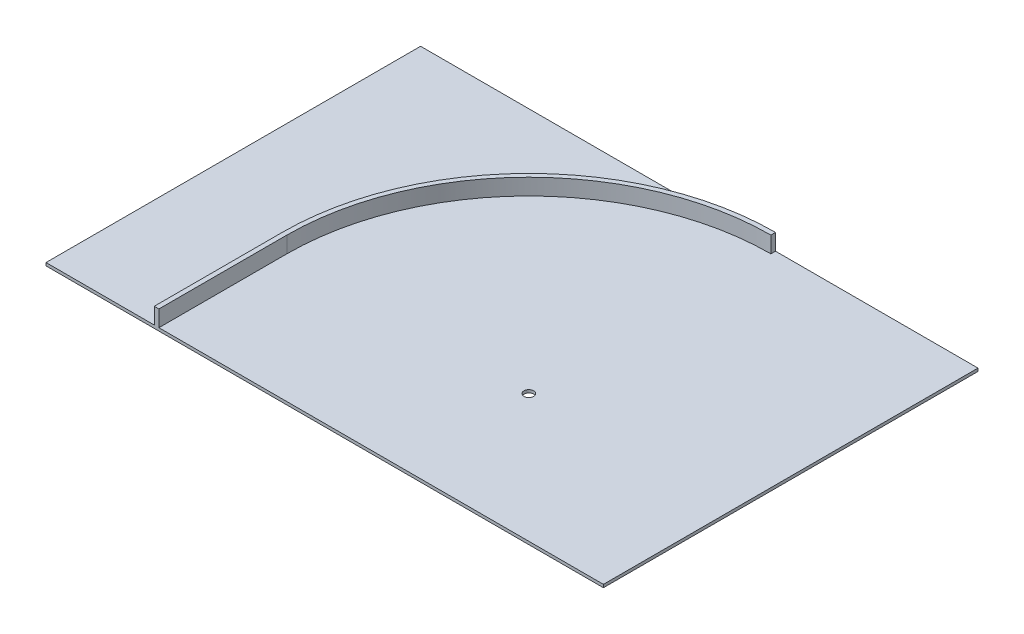
SolidWorks part; units mm, degrees
ref_plane "Front Plane" through (0, 0, 0) normal (0, 0, 1) x (1, 0, 0)
ref_plane "Top Plane" through (0, 0, 0) normal (0, 1, 0) x (1, 0, 0)
ref_plane "Right Plane" through (0, 0, 0) normal (1, 0, 0) x (0, 0, -1)
sketch "Sketch3" plane through (0, 0, 0) normal (0, 1, 0) x (1, 0, 0)
  line L0 (0, 521) -> (0, 531)
  line L1 (0, 0) -> (-839.8654, 0) construction
  line L2 (0, 0) -> (-451.1992, 260.5) construction
  line L5 (-521, 0) -> (-531, 0)
  circle A0 centre (0, 0) radius 250 construction
  arc A3 (0, 521) -> (-521, 0) centre (0, 0) ccw
  arc A4 (0, 531) -> (-531, 0) centre (0, 0) ccw
  dimension "D1" = 521
  dimension "D2" = 10
  dimension "D3" = 30
extrude "Boss-Extrude1" add sketch "Sketch3" along normal blind 35
sketch "Sketch4" plane through (0, 0, 0) normal (0, 1, 0) x (1, 0, 0)
  line L1 (-764.07, -275.4) -> (435.93, -275.4)
  line L2 (-764.07, -275.4) -> (-764.07, 531)
  line L3 (-764.07, 531) -> (435.93, 531)
  line L4 (435.93, -275.4) -> (435.93, 531)
  dimension "D1" = 1200
  dimension "D2" = 275.4
  dimension "D3" = 764.07
extrude "Boss-Extrude2" add sketch "Sketch4" against normal blind 6.35
hole_wizard "Ø20.0mm Dowel Hole1" positions "Sketch6" profile "Sketch7" hole size "Ø20.0" standard "ANSI Metric" end condition through all
sketch "Sketch6" plane through (0, 0, 0) normal (0, 1, 0) x (1, 0, 0)
  point P0 (0, 0)
sketch "Sketch7" plane through (0, 0, 0) normal (1, 0, 0) x (0, 0, 1)
  line L0 (0, 0) -> (0, 6.35)
  line L1 (0, 6.35) -> (10.5, 6.35)
  line L2 (10.5, 6.35) -> (10.5, 0)
  line L5 (10.5, 0) -> (0, 0)
  line L11 (0, -6.35) -> (0, 107.95) construction
  dimension "Thru Hole Dia." = 21
  dimension "Thru Hole Depth" = 6.35
sketch "Sketch8" plane through (0, 0, 0) normal (0, 0, 1) x (1, 0, 0)
  line L1 (-531, 35) -> (-521, 35)
  line L2 (-531, 35) -> (-531, 0)
  line L3 (-531, 0) -> (-521, 0)
  line L4 (-521, 35) -> (-521, 0)
extrude "Boss-Extrude3" add sketch "Sketch8" along normal up to surface (275.4 mm away) up to face at (-164.07, -3.175, 275.4)
